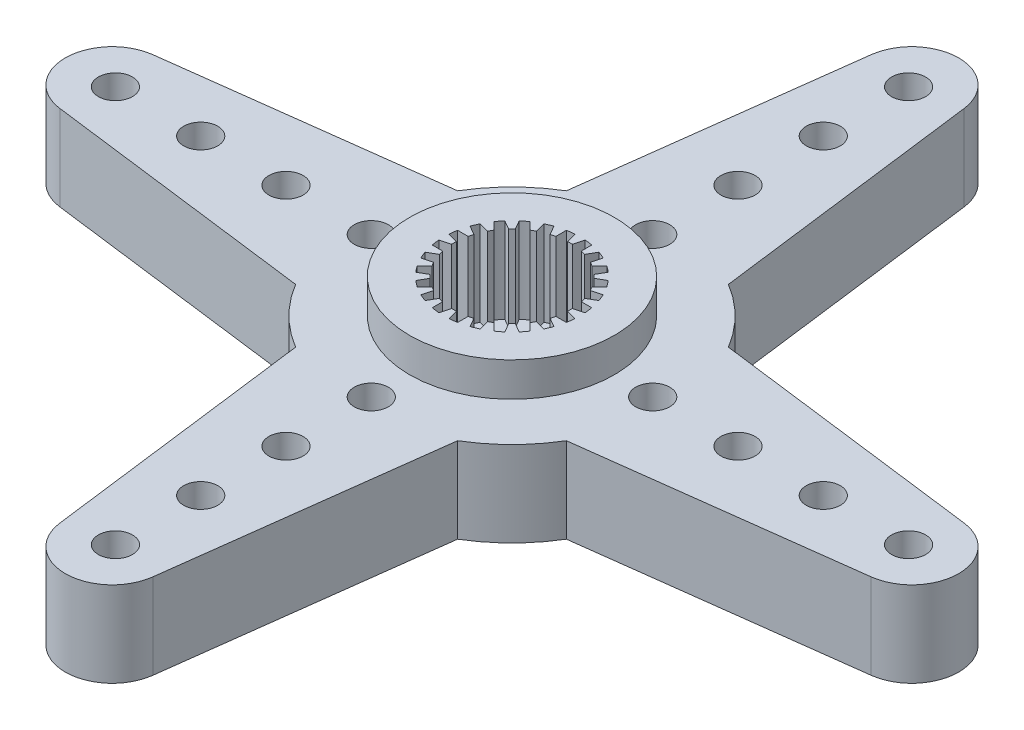
SolidWorks part; units mm, degrees
ref_plane "Plan de face" through (0, 0, 0) normal (0, 0, 1) x (1, 0, 0)
ref_plane "Plan de dessus" through (0, 0, 0) normal (0, 1, 0) x (1, 0, 0)
ref_plane "Plan de droite" through (0, 0, 0) normal (1, 0, 0) x (0, 0, -1)
sketch "Esquisse1" plane through (0, 0, 0) normal (0, 1, 0) x (1, 0, 0)
  circle A0 centre (0, 0) radius 9.25
  circle A1 centre (0, 0) radius 1.65
  dimension "D1" = 18.5
  dimension "D2" = 3.3
extrude "Boss.-Extru.1" add sketch "Esquisse1" along normal blind 8
sketch "Esquisse2" plane through (0, 8, 0) normal (0, 1, 0) x (1, 0, 0)
  line L0 (-4.75, 7.9373) -> (-2.7279, 23.7853)
  line L1 (2.7279, 23.7853) -> (4.75, 7.9373)
  line L2 (4.75, 7.9373) -> (-4.75, 7.9373)
  line L3 (-9.6717, 26.1873) -> (9.6602, 26.1873) construction
  circle A0 centre (0, 0) radius 9.25 construction
  arc A1 (-2.7279, 23.7853) -> (2.7279, 23.7853) centre (0, 23.4373) cw
  dimension "D3" = 2.75
  dimension "D1" = 9.5
  dimension "D2" = 18.25
extrude "Boss.-Extru.2" add sketch "Esquisse2" against normal up to surface (8 mm away) up to face at (0, 0, 9.25)
pattern_circular "Répétition circulaire1" count 4 over 360 about axis through (0, 8, 0) along (0, -1, 0) of "Boss.-Extru.2" reverse direction yes
sketch "Esquisse3" plane through (0, 8, 0) normal (0, 1, 0) x (1, 0, 0)
  line L0 (0, 0) -> (0, 17.0578) construction
  circle A0 centre (0, 8.25) radius 1
  dimension "D1" = 2
  dimension "D2" = 8.25
extrude "Enlèv. mat.-Extru.1" cut sketch "Esquisse3" against normal blind 8
pattern_linear "Répétition linéaire1" count 4 spacing 5 along (0, 0, -1) of "Enlèv. mat.-Extru.1"
pattern_circular "Répétition circulaire2" count 4 over 360 about axis through (0, 8, 0) along (0, -1, 0) of "Enlèv. mat.-Extru.1", "Répétition linéaire1"
sketch "Esquisse4" plane through (0, 8, 0) normal (0, 1, 0) x (1, 0, 0)
  line L1 (-37.0652, 32.1232) -> (36.96, 32.1232)
  line L2 (-37.0652, 32.1232) -> (-37.0652, -32.9644)
  line L3 (-37.0652, -32.9644) -> (36.96, -32.9644)
  line L4 (36.96, 32.1232) -> (36.96, -32.9644)
  circle A0 centre (0, 0) radius 6
  dimension "D2" = 12
extrude "Enlèv. mat.-Extru.2" cut sketch "Esquisse4" against normal blind 2
sketch "Esquisse5" plane through (0, 8, 0) normal (0, 1, 0) x (1, 0, 0)
  circle A0 centre (0, 0) radius 4
  dimension "D1" = 8
extrude "Enlèv. mat.-Extru.3" cut sketch "Esquisse5" against normal blind 5
sketch "Esquisse6" plane through (0, 8, 0) normal (0, 1, 0) x (1, 0, 0)
  line L0 (0, 0) -> (0, 6.8792) construction
  line L1 (0, 6.8792) -> (-2.9166, 4) construction
  line L2 (-2.9166, 4) -> (2.5197, 4) construction
  line L3 (-0.3, 4) -> (-0.1392, 3.4)
  line L4 (-0.1392, 3.4) -> (0.1392, 3.4)
  line L5 (0.1392, 3.4) -> (0.3, 4)
  line L6 (0.3, 4) -> (-0.3, 4)
  circle A0 centre (0, 0) radius 4 construction
  dimension "D1" = 0.6
  dimension "D2" = 0.6
  dimension "D3" = 15
extrude "Boss.-Extru.3" add sketch "Esquisse6" against normal up to surface (5 mm away) up to face at (0, 3, 1.65)
pattern_circular "Répétition circulaire3" count 24 over 360 about axis through (0, 8, 0) along (0, -1, 0) of "Boss.-Extru.3"
sketch "Esquisse7" plane through (0, 0, 0) normal (0, -1, 0) x (1, 0, 0)
  circle A0 centre (0, 0) radius 4.5
  circle A1 centre (0, 0) radius 34.023
  dimension "D1" = 9
extrude "Enlèv. mat.-Extru.4" cut sketch "Esquisse7" against normal blind 1
sketch "Esquisse8" plane through (0, 0, 0) normal (0, -1, 0) x (1, 0, 0)
  circle A0 centre (0, 0) radius 2.75
  dimension "D1" = 5.5
extrude "Enlèv. mat.-Extru.5" cut sketch "Esquisse8" against normal blind 1
chamfer "Chanfrein1" distance 1 angle 45 1 edges at (0, 1, -4.5)
